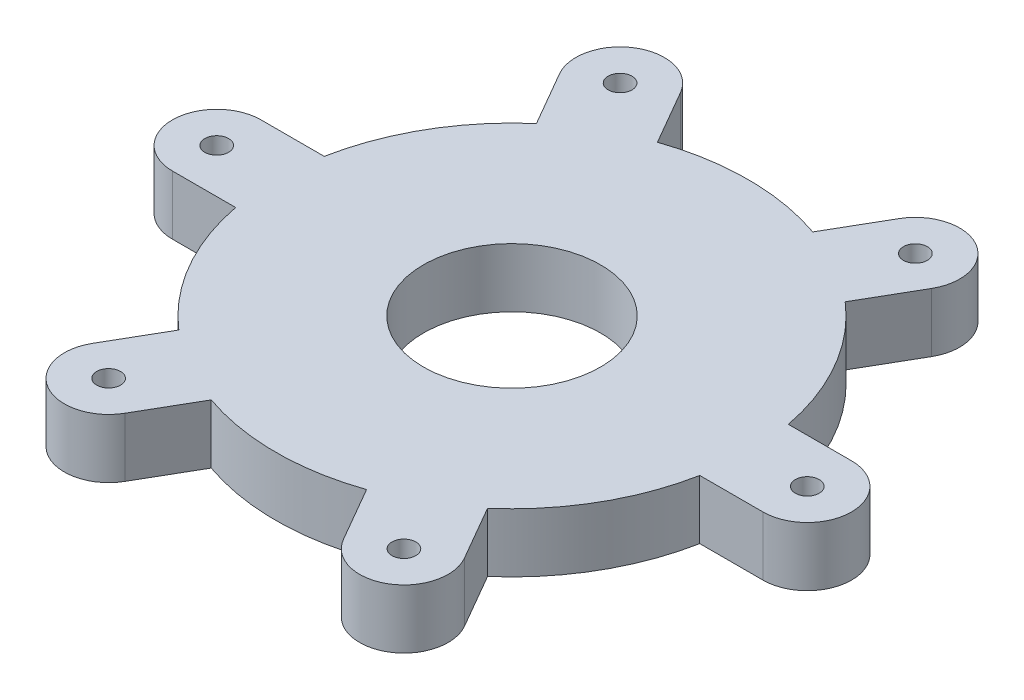
SolidWorks part; units mm, degrees
ref_plane "Front Plane" through (0, 0, 0) normal (0, 0, 1) x (1, 0, 0)
ref_plane "Top Plane" through (0, 0, 0) normal (0, 1, 0) x (1, 0, 0)
ref_plane "Right Plane" through (0, 0, 0) normal (1, 0, 0) x (0, 0, -1)
sketch "Sketch1" plane through (0, 0, 0) normal (0, 1, 0) x (1, 0, 0)
  line L0 (0, 15) -> (0, 25) construction
  circle A0 centre (0, 0) radius 25
  circle A1 centre (0, 0) radius 15
  dimension "D1" = 50
  dimension "D2" = 10
extrude "Boss-Extrude1" add sketch "Sketch1" along normal mid plane 10
sketch "Sketch6" plane through (0, 5, 0) normal (0, 1, 0) x (1, 0, 0)
  circle A0 centre (0, 0) radius 25
  circle A1 centre (0, 0) radius 40
  circle A3 centre (0, 0) radius 25 construction
  dimension "D1" = 80
extrude "Boss-Extrude3" add sketch "Sketch6" against normal blind 10
sketch "Sketch7" plane through (0, -5, 0) normal (0, -1, 0) x (1, 0, 0)
  line L0 (0, 0) -> (27.5, 0) construction
  line L1 (0, 0) -> (27.5, 0) construction
  circle A0 centre (0, 0) radius 27.5 construction
  circle A1 centre (27.5, 0) radius 7
  circle A2 centre (14.6159, 23.2943) radius 7
  circle A3 centre (-11.9636, 24.7613) radius 7
  circle A4 centre (-27.333, 3.0263) radius 7
  circle A5 centre (-17.0907, -21.5444) radius 7
  circle A6 centre (9.166, -25.9275) radius 7
  point P3 (27.5, 0)
  point P4 (14.6159, 23.2943)
  point P5 (-11.9636, 24.7613)
  point P6 (-27.333, 3.0263)
  point P7 (-17.0907, -21.5444)
  point P8 (9.166, -25.9275)
  point P22 (0, 0)
  dimension "D1" = 55
  dimension "D8" = 14
  dimension "D2" = 26.62
  dimension "D3" = 26.62
  dimension "D4" = 26.62
  dimension "D5" = 26.62
  dimension "D6" = 0
  dimension "D7" = 26.62
extrude "Cut-Extrude1" cut sketch "Sketch7" against normal blind 5
sketch "Sketch8" plane through (0, 5, 0) normal (0, 1, 0) x (1, 0, 0)
  line L0 (50, 7.5) -> (39.2906, 7.5)
  line L2 (39.2906, -7.5) -> (50, -7.5)
  line L3 (39.2906, -7.5) -> (39.2906, 7.5)
  circle A0 centre (0, 0) radius 57.5 construction
  arc A1 (50, -7.5) -> (50, 7.5) centre (50, 0) ccw
  circle A3 centre (0, 0) radius 40 construction
  dimension "D1" = 115
  dimension "D2" = 15
extrude "Boss-Extrude4" add sketch "Sketch8" against normal up to surface (10 mm away) up to face at (14.6159, -5, 16.2943)
sketch "Sketch10" plane through (0, 5, 0) normal (0, 1, 0) x (1, 0, 0)
  circle A0 centre (0, 0) radius 50 construction
  point P3 (50, 0)
  dimension "D1" = 100
hole_wizard "Tap Drill for #10-32 Tap1" positions "Sketch11" profile "Sketch12" hole size "#10-32" standard "ANSI Inch" end condition up to next
sketch "Sketch11" plane through (0, 5, 0) normal (0, 1, 0) x (1, 0, 0)
  point P0 (50, 0)
sketch "Sketch12" plane through (50, 5, 0) normal (1, 0, 0) x (0, 0, 1)
  line L0 (0, 0) -> (0, 10)
  line L1 (0, 10) -> (2.0193, 10)
  line L2 (2.0193, 10) -> (2.0193, 0)
  line L5 (2.0193, 0) -> (0, 0)
  line L11 (0, -6.35) -> (0, 107.95) construction
  dimension "Thru Hole Dia." = 4.0386
  dimension "Thru Hole Depth" = 10
pattern_circular "CirPattern1" count 6 over 360 about axis through (0, 5, 0) along (0, -1, 0) of "Tap Drill for #10-32 Tap1", "Boss-Extrude4"
equation "\"GEARDIST\"=26.62"
equation "\"D2@Sketch7\"=\"GEARDIST\""
equation "\"D3@Sketch7\"=\"GEARDIST\""
equation "\"D4@Sketch7\"=\"GEARDIST\""
equation "\"D5@Sketch7\"=\"GEARDIST\""
equation "\"D7@Sketch7\"=\"GEARDIST\""
